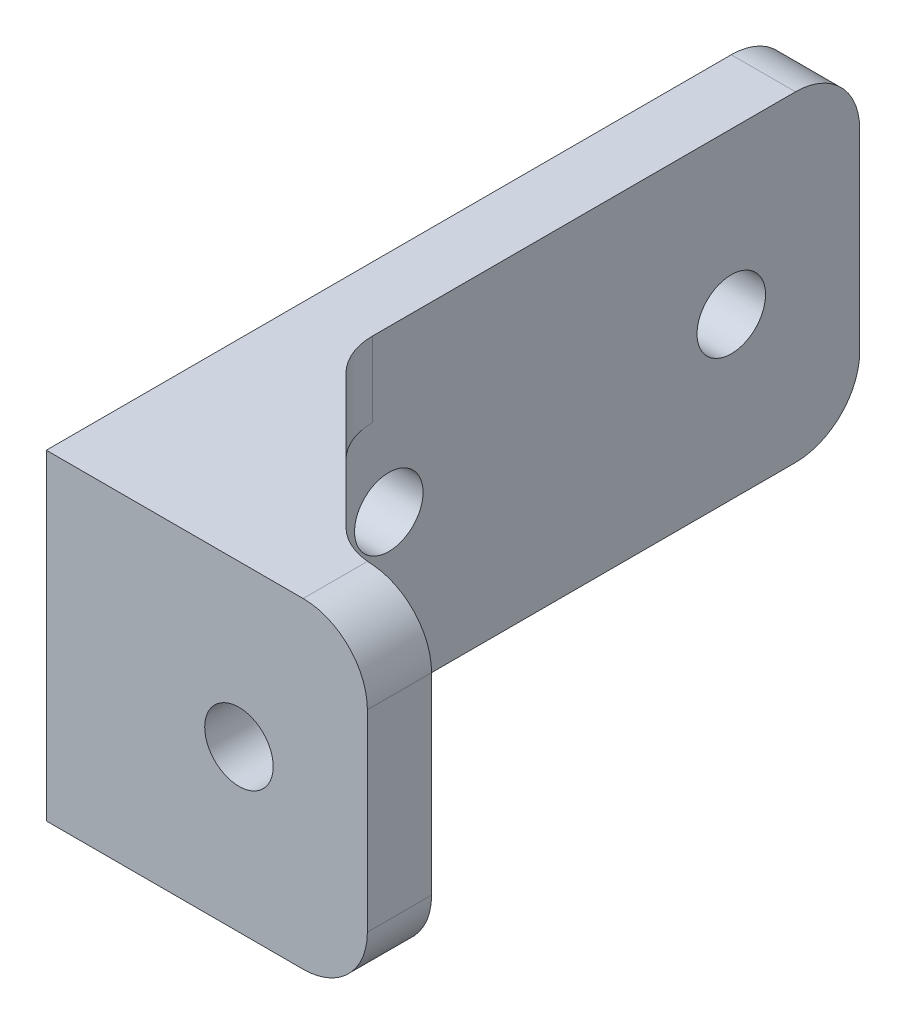
SolidWorks part; units mm, degrees
ref_plane "Front Plane" through (0, 0, 0) normal (0, 0, 1) x (1, 0, 0)
ref_plane "Top Plane" through (0, 0, 0) normal (0, 1, 0) x (1, 0, 0)
ref_plane "Right Plane" through (0, 0, 0) normal (1, 0, 0) x (0, 0, -1)
sketch "Sketch1" plane through (0, 0, 0) normal (0, 1, 0) x (1, 0, 0)
  line L1 (0, 0) -> (3, 0)
  line L2 (0, 0) -> (0, 35)
  line L3 (0, 35) -> (3, 35)
  line L4 (3, 0) -> (3, 35)
  line L5 (0, 0) -> (15, 0)
  line L6 (0, 0) -> (0, 3)
  line L7 (0, 3) -> (15, 3)
  line L8 (15, 0) -> (15, 3)
  dimension "D1" = 35
  dimension "D2" = 15
  dimension "D3" = 3
  dimension "D4" = 3
extrude "Boss-Extrude1" add sketch "Sketch1" along normal blind 15 contours L2 L7 L4 L3 | L7 L2 L1 L4 | L5 L8 L7 L4 region at (1.5, 0, -1.5) region at (9, 0, -1.5) region at (1.5, 0, -19)
sketch "Sketch2" plane through (0, 0, -3) normal (0, 0, -1) x (-1, 0, 0)
  line L0 (-9, 15) -> (-9, 0) construction
  line L1 (-3, 15) -> (-15, 15) construction
  line L2 (-3, 0) -> (-15, 0) construction
  circle A0 centre (-9, 7.5) radius 1.6
  dimension "D1" = 3.2
extrude "Cut-Extrude1" cut sketch "Sketch2" against normal through all
sketch "Sketch3" plane through (3, 0, 0) normal (1, 0, 0) x (0, 0, -1)
  line L0 (3, 7.5) -> (35, 7.5) construction
  line L1 (3, 15) -> (3, 0) construction
  line L2 (35, 15) -> (35, 0) construction
  line L3 (3, 15) -> (3, 0) construction
  circle A0 centre (13, 7.5) radius 1.6
  circle A1 centre (29, 7.5) radius 1.6
  dimension "D1" = 10
  dimension "D2" = 6
  dimension "D3" = 3.2
extrude "Cut-Extrude2" cut sketch "Sketch3" against normal through all
fillet "Fillet1" radius 3 4 edges at (1.5, 15, -35) (1.5, 0, -35) (15, 15, -1.5) (15, 0, -1.5)
chamfer "Chamfer1" distance 8 angle 45 1 edges at (3, 7.5, -3)
sketch "Sketch6" plane through (15, 0, 0) normal (1, 0, 0) x (0, 0, -1)
  line L0 (3, 12) -> (3, 3) construction
  line L1 (3, 11.5) -> (11, 11.5)
  line L2 (3, 11.5) -> (3, 3.5)
  line L3 (3, 3.5) -> (11, 3.5)
  line L4 (11, 11.5) -> (11, 3.5)
  line L5 (11, 15) -> (11, 0) construction
  line L6 (3, 7.5) -> (0, 7.5) construction
  line L7 (0, 12) -> (0, 3) construction
  dimension "D1" = 8
extrude "Cut-Extrude5" cut sketch "Sketch6" against normal up to surface (12 mm away) up to face at (3, 7.5, -14.6)
fillet "Fillet2" radius 3 5 edges at (3, 7.5, -3) (11, 1.75, -3) (3, 1.75, -11) (3, 13.25, -11) (11, 13.25, -3)
